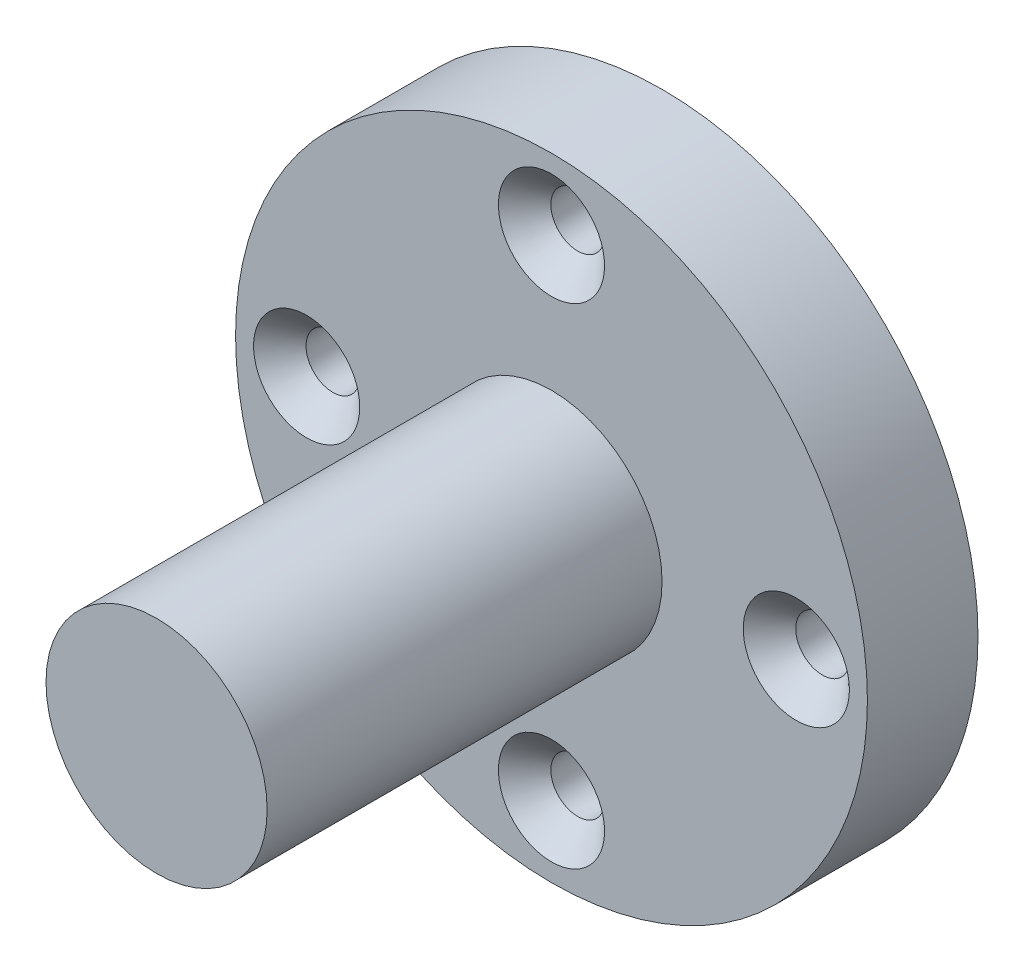
SolidWorks part; units mm, degrees
material "6063-T5"
ref_plane "Front" through (0, 0, 0) normal (0, 0, 1) x (1, 0, 0)
ref_plane "Top" through (0, 0, 0) normal (0, 1, 0) x (1, 0, 0)
ref_plane "Right" through (0, 0, 0) normal (1, 0, 0) x (0, 0, -1)
sketch "Croquis1" plane through (0, 0, 0) normal (0, 0, 1) x (1, 0, 0)
  circle A0 centre (0, 0) radius 20
  dimension "D1" = 40
extrude "Saliente-Extruir1" add sketch "Croquis1" along normal blind 7
hole_wizard "Refrentado para tornillo tapón con cabeza plana de clavija de M31" positions "Croquis2" profile "Croquis4" countersink size "M3" standard "Ansi Metric" end condition up to next
sketch "Croquis2" plane through (0, 0, 7) normal (0, 0, 1) x (1, 0, 0)
  line L0 (0, -55) -> (0, 55) construction
  point P0 (0, 15.5)
  point P12 (15.5, 0)
  point P13 (0, -15.5)
  point P14 (-15.5, 0)
  dimension "D1" = 4
sketch "Croquis4" plane through (0, 15.5, 7) normal (1, 0, 0) x (0, -1, 0)
  line L0 (0, 0) -> (0, 7)
  line L1 (0, 7) -> (1.7, 7)
  line L2 (1.7, 7) -> (1.7, 1.66)
  line L3 (1.7, 1.66) -> (3.36, 0)
  line L5 (3.36, 0) -> (0, 0)
  line L6 (-1.7, 1.66) -> (-3.36, 0) construction
  line L11 (0, -6.35) -> (0, 107.95) construction
  dimension "Diámetro de taladro hasta el siguiente" = 3.4
  dimension "Profundidad de taladro hasta el siguiente" = 7
  dimension "Diámetro de avellanado cercano" = 6.72
  dimension "Ángulo de avellanado cercano" = 90
hole_wizard "Taladro de margen para M31" positions "Croquis5" profile "Croquis7" hole size "M3" standard "Ansi Metric" end condition up to next
sketch "Croquis5" plane through (0, 0, 7) normal (0, 0, 1) x (1, 0, 0)
  point P0 (0, 0)
sketch "Croquis7" plane through (0, 0, 7) normal (1, 0, 0) x (0, -1, 0)
  line L0 (0, 0) -> (0, 7)
  line L1 (0, 7) -> (1.7, 7)
  line L2 (1.7, 7) -> (1.7, 0)
  line L5 (1.7, 0) -> (0, 0)
  line L11 (0, -6.35) -> (0, 107.95) construction
  dimension "Diámetro de taladro hasta el siguiente" = 3.4
  dimension "Profundidad de taladro hasta el siguiente" = 7
sketch "Croquis8" plane through (0, 0, 0) normal (0, 0, -1) x (-1, 0, 0)
  circle A0 centre (0, 0) radius 5
  dimension "D1" = 10
extrude "Cortar-Extruir1" cut sketch "Croquis8" against normal blind 3
sketch "Croquis9" plane through (0, 0, 7) normal (0, 0, 1) x (1, 0, 0)
  circle A0 centre (0, 0) radius 7
  dimension "D1" = 14
extrude "Saliente-Extruir2" add sketch "Croquis9" along normal blind 25
